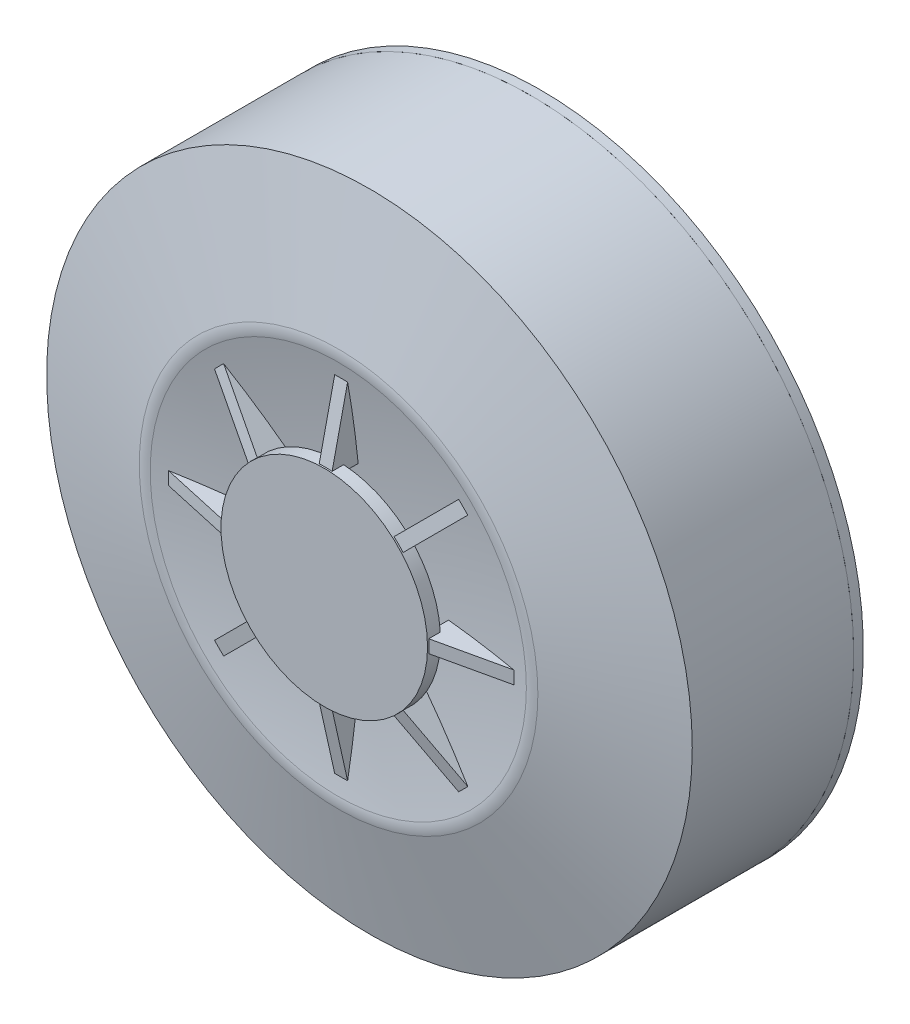
SolidWorks part; units mm, degrees
ref_plane "Front Plane" through (0, 0, 0) normal (0, 0, 1) x (1, 0, 0)
ref_plane "Top Plane" through (0, 0, 0) normal (0, 1, 0) x (1, 0, 0)
ref_plane "Right Plane" through (0, 0, 0) normal (1, 0, 0) x (0, 0, -1)
sketch "Sketch1" plane through (0, 0, 0) normal (0, 0, 1) x (1, 0, 0)
  circle A0 centre (0, 0) radius 50
  dimension "D1" = 100
extrude "Boss-Extrude1" add sketch "Sketch1" along normal blind 30
sketch "Sketch2" plane through (0, 0, 0) normal (0, 1, 0) x (1, 0, 0)
  line L0 (-50, -25) -> (-30, -30)
  line L1 (-50, 0) -> (-50, -30) construction
  line L2 (-50, -30) -> (50, -30) construction
  line L3 (0, -27) -> (15.8825, -27) construction
  line L4 (-50, -25) -> (-56.6853, -25)
  line L5 (-56.6853, -25) -> (-56.6853, -49.3656)
  line L6 (-56.6853, -49.3656) -> (0, -49.3656)
  line L7 (0, -49.3656) -> (0, -27)
  arc A0 (-30, -30) -> (0, -27) centre (0, -178.5) cw
  point P8 (0, -30)
  dimension "D1" = 5
  dimension "D2" = 30
  dimension "D3" = 3
revolve "Cut-Revolve1" cut sketch "Sketch2" angle 360 about L7
fillet "Fillet1" radius 4 1 edges at (30, 0, 30)
shell "Shell1" thickness 2 removed face at (50, 0, 0)
sketch "Sketch3" plane through (0, 0, 0) normal (0, 0, 1) x (1, 0, 0)
  circle A0 centre (0, 0) radius 12.5
  dimension "D1" = 25
extrude "Cut-Extrude1" cut sketch "Sketch3" along normal through all
ref_plane "Plane1" through (0, 0, 30) normal (0, 0, 1) x (1, 0, 0)
sketch "Sketch4" plane through (0, 0, 30) normal (0, 0, 1) x (1, 0, 0)
  circle A0 centre (0, 0) radius 15
  dimension "D1" = 30
extrude "Boss-Extrude2" add sketch "Sketch4" along normal blind 2 separate body
sketch "Sketch5" plane through (0, 0, 0) normal (0, 1, 0) x (0, 0, -1)
  line L0 (-32, 15) -> (-29.1012, 28)
  line L1 (-32, 15) -> (-27.2419, 15)
  line L13 (-29.4876, 29.9882) -> (-24.5, 49.9384)
  line L14 (-24.5, 49.9384) -> (-24.5, 57.1853)
  line L15 (-24.5, 57.1853) -> (-49.8656, 57.1853)
  line L16 (-49.8656, 57.1853) -> (-49.8656, -0.5)
  line L17 (-49.8656, -0.5) -> (-26.5008, -0.5)
  arc A3 (-26.5008, -0.5) -> (-29.4876, 29.9882) centre (-178.5, 0) ccw
  arc A4 (-27.2419, 15) -> (-29.1012, 28) centre (-178.5, 0) ccw
  dimension "D1" = 13
  dimension "D2" = 0.5
extrude "Boss-Extrude3" add sketch "Sketch5" along normal mid plane 2
pattern_circular "CirPattern1" count 8 over 360 about axis through (0, 0, 32) along (0, 0, -1) of "Boss-Extrude3"
sketch "Sketch7" plane through (0, 0, 0) normal (0, 0, -1) x (-1, 0, 0)
  circle A0 centre (0, 0) radius 48 construction
  circle A1 centre (0, 0) radius 48
  circle A2 centre (0, 0) radius 49
  dimension "D1" = 1
extrude "Cut-Extrude2" cut sketch "Sketch7" against normal blind 1
sketch "Sketch8" plane through (0, 0, 0) normal (0, 0, -1) x (-1, 0, 0)
  circle A0 centre (0, 0) radius 50 construction
  circle A1 centre (0, 0) radius 50
extrude "Boss-Extrude4" add sketch "Sketch8" along normal blind 1.5 separate body
sketch "Sketch9" plane through (0, 0, 0) normal (0, 0, 1) x (1, 0, 0)
  circle A1 centre (0, 0) radius 48
  circle A2 centre (0, 0) radius 49
  circle A3 centre (0, 0) radius 49
  dimension "D1" = 1
  dimension "D2" = 1
extrude "Boss-Extrude5" add sketch "Sketch9" along normal blind 1
other "Move Face1" face at (15, 0, 30) offset 1 parameters "D1"=1
combine bodies "Combine2" operation type add bodies to combine 110 107
